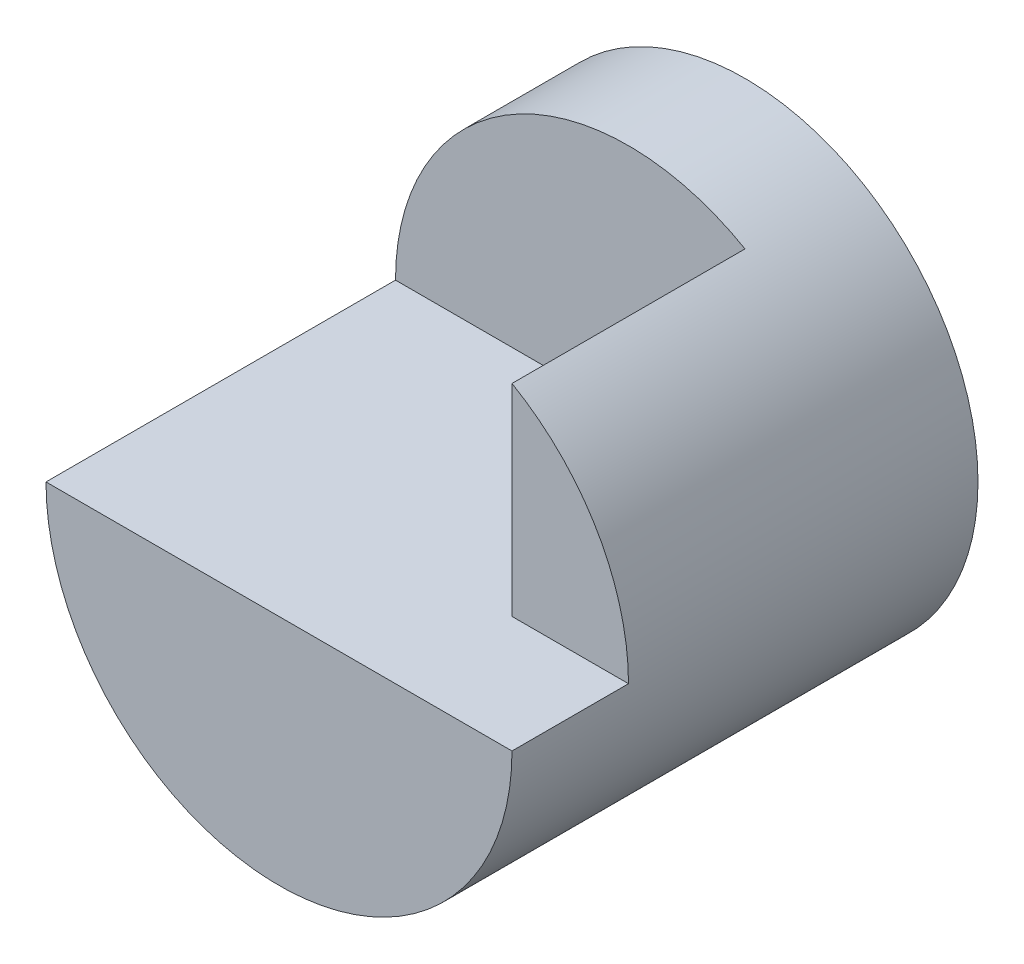
SolidWorks part; units mm, degrees
ref_plane "Front Plane" through (0, 0, 0) normal (0, 0, 1) x (1, 0, 0)
ref_plane "Top Plane" through (0, 0, 0) normal (0, 1, 0) x (1, 0, 0)
ref_plane "Right Plane" through (0, 0, 0) normal (1, 0, 0) x (0, 0, -1)
sketch "Sketch1" plane through (0, 0, 0) normal (0, 0, 1) x (1, 0, 0)
  circle A0 centre (0, 0) radius 20
  dimension "D1" = 40
extrude "Boss-Extrude1" add sketch "Sketch1" along normal blind 40
sketch "Sketch2" plane through (0, 0, 0) normal (1, 0, 0) x (0, 0, -1)
  line L0 (0, 20) -> (-40, 20) construction
  line L1 (-10, 20) -> (-40, 20)
  line L2 (-10, 20) -> (-10, 18)
  line L3 (-10, 18) -> (-40, 18)
  line L4 (-40, 20) -> (-40, 18)
  line L5 (-40, 20) -> (-40, -20) construction
  dimension "D1" = 30
  dimension "D2" = 2
extrude "Cut-Extrude1" cut sketch "Sketch2" along normal blind 40 and the other way blind 40
sketch "Sketch3" plane through (0, 0, 0) normal (1, 0, 0) x (0, 0, -1)
  line L0 (-40, 18) -> (-40, -20) construction
  line L1 (-40, 20) -> (-30, 20)
  line L2 (-40, 20) -> (-40, 0)
  line L3 (-40, 0) -> (-30, 0)
  line L4 (-30, 20) -> (-30, 0)
  dimension "D1" = 20
  dimension "D2" = 0
  dimension "D3" = 10
  dimension "D4" = 20
extrude "Cut-Extrude2" cut sketch "Sketch3" against normal blind 40 and the other way blind 40
sketch "Sketch4" plane through (0, 0, 0) normal (0, 1, 0) x (1, 0, 0)
  line L0 (-20, -10) -> (10, -10)
  line L1 (-20, 0) -> (-20, -30) construction
  line L2 (10, -10) -> (10, -30)
  line L3 (10, -30) -> (20, -30)
  line L4 (20, -30) -> (20, 0) construction
  line L5 (20, -30) -> (20, 0)
  line L6 (20, 0) -> (-20, 0)
  line L7 (-20, 0) -> (-20, -10)
  line L8 (-20, -10) -> (-20, -30)
  line L9 (-20, -30) -> (10, -30)
  dimension "D1" = 10
  dimension "D2" = 20
  dimension "D3" = 10
extrude "Cut-Extrude4" cut sketch "Sketch4" along normal blind 40 contours L8 L9 L2 L0 region at (-5, 0, 20)
